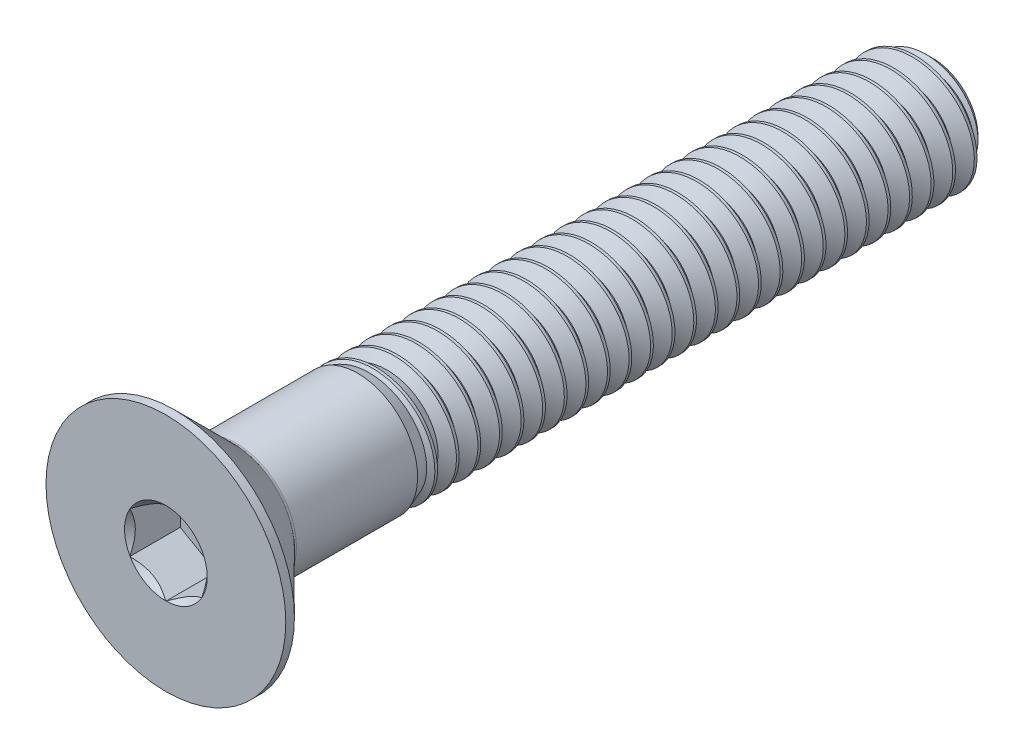
SolidWorks part; units mm, degrees
ref_plane "Front Plane" through (0, 0, 0) normal (0, 0, 1) x (1, 0, 0)
ref_plane "Top Plane" through (0, 0, 0) normal (0, 1, 0) x (1, 0, 0)
ref_plane "Right Plane" through (0, 0, 0) normal (1, 0, 0) x (0, 0, -1)
sketch "Sketch1" plane through (0, 0, 0) normal (0, 0, 1) x (1, 0, 0)
  line L1 (-0.75, 0.433) -> (-0.75, -0.433) construction
  line L2 (-0.75, -0.433) -> (0, -0.866) construction
  line L3 (0, -0.866) -> (0.75, -0.433) construction
  line L4 (0.75, -0.433) -> (0.75, 0.433) construction
  line L5 (0.75, 0.433) -> (0, 0.866) construction
  line L6 (0, 0.866) -> (-0.75, 0.433) construction
  circle A0 centre (0, 0) radius 2.5 construction
  circle A1 centre (0, 0) radius 0.75 construction
  circle A2 centre (0, 0) radius 0.8625 construction
  point P11 (0, 2.5)
  dimension "Head Diameter" = 5
  dimension "Hex Countersink" = 1.725
  dimension "Drive Size" = 1.5
sketch "Sketch2" plane through (0, 0, 0) normal (1, 0, 0) x (0, 0, -1)
  line L0 (0, 0) -> (16, 0) construction
  line L1 (0.18, 2.5) -> (1.5, 1.18) construction
  line L2 (16, 1.25) -> (4, 1.25) construction
  line L3 (0.18, 2.5) -> (0, 2.5) construction
  line L4 (0, 2.5) -> (0, -2.5) construction
  line L5 (0, 0) -> (0, 2.5) construction
  line L6 (0.18, -2.5) -> (1.5, -1.18) construction
  line L7 (16, 1.25) -> (16, -1.25) construction
  line L8 (15.9719, 1.2987) -> (16.4219, 1.2987) construction
  line L9 (16.4219, 1.2987) -> (16.1969, 0.909) construction
  line L10 (16.1969, 0.909) -> (15.9719, 1.2987) construction
  line L11 (15.9859, 1.2744) -> (16.4078, 1.2744) construction
  line L12 (16, 1.25) -> (16.3938, 1.25) construction
  line L13 (16.1688, 0.9577) -> (16.225, 0.9577) construction
  line L14 (16.1969, 1.2987) -> (16.1969, 1.25) construction
  line L15 (16.1969, 0.9577) -> (16.1969, 0.909) construction
  point P16 (16, 0)
  point P20 (1.05, 0)
  point P27 (16.1969, 1.2744)
  point P28 (14.425, -1.25)
  dimension "Edge Length" = 0.18
  dimension "Countersink Angle" = 90
  dimension "Head Height" = 1.5
  dimension "Thread Size" = 2.5
  dimension "Minimum Thread Length" = 12
  dimension "Length" = 16
  dimension "D1" = 60
  dimension "Thread Pitch" = 0.45
  dimension "D2" = 0.0563
  dimension "Hex Drive Depth" = 1.05
  dimension "D3" = 1.575
sketch "Sketch3" plane through (0, 0, 0) normal (1, 0, 0) x (0, 0, -1)
  line L0 (0.18, 2.5) -> (1.5, 1.18) construction
  line L1 (1.5, 1.18) -> (4, 1.18) construction
  line L2 (0, 0) -> (16, 0) construction
  arc A0 (1.4707, 1.2093) -> (1.5414, 1.18) centre (1.5414, 1.28) ccw construction
  point P8 (2.5, 0)
  point P9 (3, 0)
  dimension "Head Radius" = 0.1
  dimension "D1" = 1
  dimension "D2" = 1
sketch "Sketch4" plane through (0, 0, 0) normal (1, 0, 0) x (0, 0, -1)
  line L0 (1.43, 1.25) -> (0.18, 2.5)
  line L1 (0.18, 2.5) -> (0, 2.5)
  line L2 (0, 2.5) -> (0, 0)
  line L3 (0, 0) -> (16, 0)
  line L4 (16, 1.25) -> (16, -1.25) construction
  line L5 (16, 0) -> (16, 0.935)
  line L6 (16, 0.935) -> (15.685, 1.25)
  line L7 (16, 1.25) -> (4, 1.25) construction
  line L8 (15.685, 1.25) -> (1.43, 1.25)
  line L9 (0.18, 2.5) -> (1.5, 1.18) construction
  dimension "D1" = 45
  dimension "D2" = 0.315
revolve "Revolve1" add sketch "Sketch4" angle 360 about L0
sketch "Sketch5" plane through (0, 0, 0) normal (0, 0, 1) x (1, 0, 0)
  line L0 (-0.75, 0.433) -> (-0.75, -0.433) construction
  line L1 (-0.75, 0.433) -> (-0.75, -0.433)
  line L2 (-0.75, -0.433) -> (0, -0.866)
  line L3 (0, -0.866) -> (0.75, -0.433)
  line L4 (0.75, -0.433) -> (0.75, 0.433)
  line L5 (0.75, 0.433) -> (0, 0.866)
  line L6 (0, 0.866) -> (-0.75, 0.433)
  circle A0 centre (0, 0) radius 0.75 construction
  circle A1 centre (0, 0) radius 0.75 construction
extrude "Cut-Extrude1" cut sketch "Sketch5" against normal up to vertex (1.05 mm away) up to point (0, 0, -1.05)
sketch "Sketch6" plane through (0, 0, 0) normal (0, 0, 1) x (1, 0, 0)
  circle A0 centre (0, 0) radius 0.8625
  circle A1 centre (0, 0) radius 0.8625 construction
extrude "Cut-Extrude2" cut sketch "Sketch6" against normal up to vertex (1.05 mm away) draft 45 up to point (0, 0, -1.05)
fillet "Fillet1" radius 0.1 1 edges at (0, -1.25, -1.43)
sketch "Sketch7" plane through (0, 0, 0) normal (1, 0, 0) x (0, 0, -1)
  line L0 (15.9859, 1.2744) -> (16.4078, 1.2744)
  line L1 (16.4078, 1.2744) -> (16.225, 0.9577)
  line L2 (16.225, 0.9577) -> (16.1688, 0.9577)
  line L3 (16.1688, 0.9577) -> (15.9859, 1.2744)
sketch "Sketch8" plane through (0, 0, -16) normal (0, 0, -1) x (-1, 0, 0)
  circle A0 centre (0, 0) radius 1.25
curve "Helix/Spiral1" pitch 0.45 height 12.45 radius 1.25 centre (0, 0, -16) axis (0, 0, 1) start towards (0, 1, 0)
sweep "Cut-Sweep1" cut profiles "Sketch7" path "Helix/Spiral1" align with end faces yes
ref_plane "Plane1" through (0, 0, -4) normal (0, 0, 1) x (1, 0, 0)
sketch "Sketch9" plane through (0, 0, -4) normal (0, 0, 1) x (1, 0, 0)
  circle A0 centre (0, 0) radius 1.25
extrude "Boss-Extrude1" add sketch "Sketch9" along normal blind 0.9 and the other way blind 1.35 draft 20
equation "\"D2@Sketch2\"=\"Thread Pitch@Sketch2\"/8"
equation "\"D2@Sketch4\"=\"Thread Pitch@Sketch2\"*.7"
equation "\"D4@Helix/Spiral1\"=\"Thread Pitch@Sketch2\""
equation "\"D3@Helix/Spiral1\"=\"Minimum Thread Length@Sketch2\"+\"Thread Pitch@Sketch2\""
equation "\"D2@Boss-Extrude1\"=\"Thread Pitch@Sketch2\"*3"
equation "\"D1@Boss-Extrude1\"=\"Thread Pitch@Sketch2\"*2"
equation "\"D3@Sketch2\"=\"Thread Pitch@Sketch2\"*3.5"
equation "\"D1@Fillet1\"=\"Head Radius@Sketch3\""
equation "\"D2@Sketch3\"=\"D1@Sketch3\""
equation "\"D1@Sketch3\"=if(\"Length@Sketch2\"<25,1,4)"
